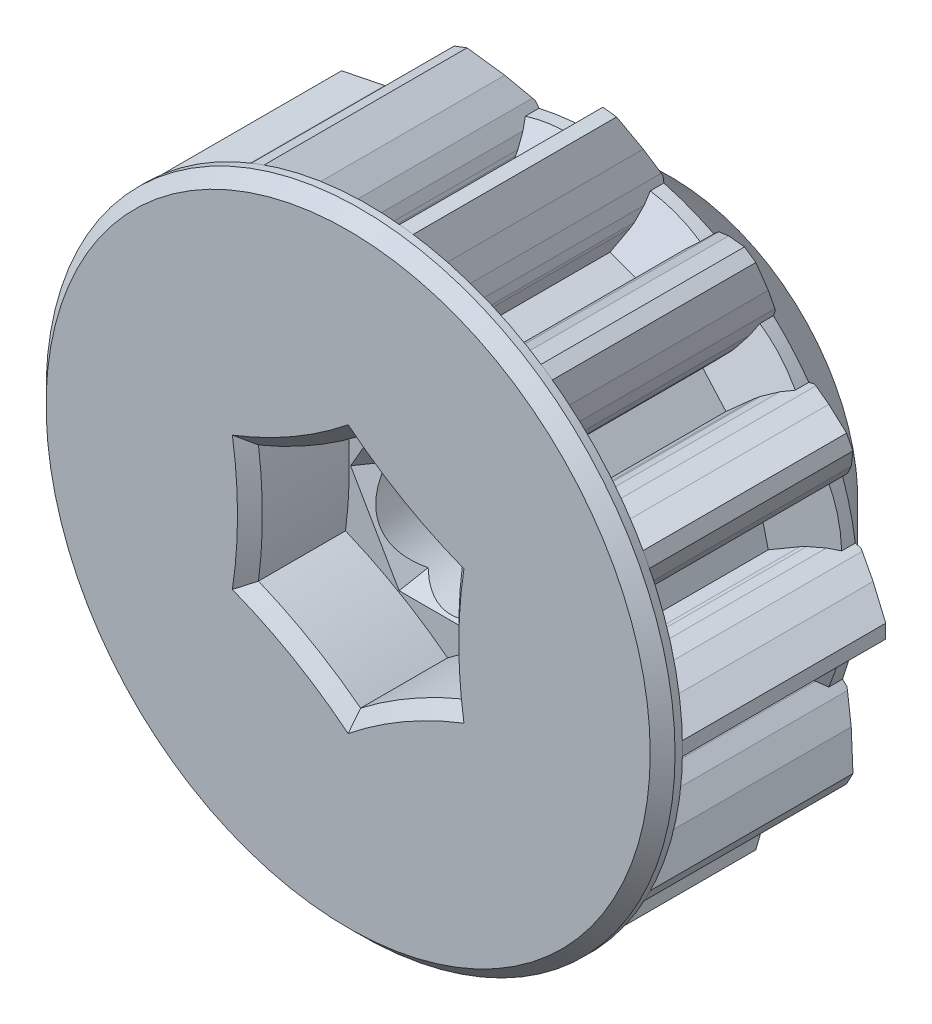
SolidWorks part; units mm, degrees
material "Custom Plastic"
ref_plane "Front Plane" through (0, 0, 0) normal (0, 0, 1) x (1, 0, 0)
ref_plane "Top Plane" through (0, 0, 0) normal (0, 1, 0) x (1, 0, 0)
ref_plane "Right Plane" through (0, 0, 0) normal (1, 0, 0) x (0, 0, -1)
sketch "Model" plane through (0, 0, 0) normal (0, 0, 1) x (1, 0, 0)
  line L0 (-12.322, -2.752) -> (-11.499, -1.837)
  line L1 (-11.499, -1.837) -> (-10.75, -1.243)
  line L2 (-10.75, -1.243) -> (-10.152, -0.913)
  line L3 (-10.152, -0.913) -> (-9.766, -0.777)
  line L4 (-9.766, -0.777) -> (-9.632, -0.751)
  line L5 (-9.632, -0.751) -> (-8.992, -0.701)
  line L6 (-8.992, -0.701) -> (-8.992, 0.701)
  line L7 (-8.992, 0.701) -> (-9.632, 0.751)
  line L8 (-9.632, 0.751) -> (-9.766, 0.777)
  line L9 (-9.766, 0.777) -> (-10.152, 0.913)
  line L10 (-10.152, 0.913) -> (-10.75, 1.243)
  line L11 (-10.75, 1.243) -> (-11.499, 1.837)
  line L12 (-11.499, 1.837) -> (-12.322, 2.752)
  line L13 (-12.322, 2.752) -> (-12.189, 3.29)
  line L14 (-12.189, 3.29) -> (-11.036, 3.717)
  line L15 (-11.036, 3.717) -> (-10.096, 3.895)
  line L16 (-10.096, 3.895) -> (-9.414, 3.91)
  line L17 (-9.414, 3.91) -> (-9.008, 3.851)
  line L18 (-9.008, 3.851) -> (-8.878, 3.811)
  line L19 (-8.878, 3.811) -> (-8.288, 3.558)
  line L20 (-8.288, 3.558) -> (-7.637, 4.8)
  line L21 (-7.637, 4.8) -> (-8.18, 5.141)
  line L22 (-8.18, 5.141) -> (-8.286, 5.226)
  line L23 (-8.286, 5.226) -> (-8.565, 5.527)
  line L24 (-8.565, 5.527) -> (-8.941, 6.096)
  line L25 (-8.941, 6.096) -> (-9.328, 6.971)
  line L26 (-9.328, 6.971) -> (-9.631, 8.163)
  line L27 (-9.631, 8.163) -> (-9.264, 8.577)
  line L28 (-9.264, 8.577) -> (-8.045, 8.42)
  line L29 (-8.045, 8.42) -> (-7.129, 8.141)
  line L30 (-7.129, 8.141) -> (-6.519, 7.837)
  line L31 (-6.519, 7.837) -> (-6.187, 7.596)
  line L32 (-6.187, 7.596) -> (-6.09, 7.501)
  line L33 (-6.09, 7.501) -> (-5.685, 7.002)
  line L34 (-5.685, 7.002) -> (-4.532, 7.799)
  line L35 (-4.532, 7.799) -> (-4.854, 8.354)
  line L36 (-4.854, 8.354) -> (-4.908, 8.478)
  line L37 (-4.908, 8.478) -> (-5.016, 8.874)
  line L38 (-5.016, 8.874) -> (-5.084, 9.553)
  line L39 (-5.084, 9.553) -> (-5.02, 10.508)
  line L40 (-5.02, 10.508) -> (-4.735, 11.704)
  line L41 (-4.735, 11.704) -> (-4.217, 11.9)
  line L42 (-4.217, 11.9) -> (-3.21, 11.194)
  line L43 (-3.21, 11.194) -> (-2.529, 10.522)
  line L44 (-2.529, 10.522) -> (-2.13, 9.968)
  line L45 (-2.13, 9.968) -> (-1.948, 9.601)
  line L46 (-1.948, 9.601) -> (-1.907, 9.471)
  line L47 (-1.907, 9.471) -> (-1.78, 8.842)
  line L48 (-1.78, 8.842) -> (-0.388, 9.011)
  line L49 (-0.388, 9.011) -> (-0.416, 9.652)
  line L50 (-0.416, 9.652) -> (-0.406, 9.788)
  line L51 (-0.406, 9.788) -> (-0.317, 10.189)
  line L52 (-0.317, 10.189) -> (-0.062, 10.821)
  line L53 (-0.062, 10.821) -> (0.438, 11.637)
  line L54 (0.438, 11.637) -> (1.246, 12.563)
  line L55 (1.246, 12.563) -> (1.796, 12.497)
  line L56 (1.796, 12.497) -> (2.36, 11.404)
  line L57 (2.36, 11.404) -> (2.65, 10.492)
  line L58 (2.65, 10.492) -> (2.746, 9.817)
  line L59 (2.746, 9.817) -> (2.737, 9.407)
  line L60 (2.737, 9.407) -> (2.713, 9.273)
  line L61 (2.713, 9.273) -> (2.533, 8.657)
  line L62 (2.533, 8.657) -> (3.845, 8.16)
  line L63 (3.845, 8.16) -> (4.118, 8.74)
  line L64 (4.118, 8.74) -> (4.189, 8.856)
  line L65 (4.189, 8.856) -> (4.454, 9.169)
  line L66 (4.454, 9.169) -> (4.974, 9.611)
  line L67 (4.974, 9.611) -> (5.796, 10.101)
  line L68 (5.796, 10.101) -> (6.942, 10.545)
  line L69 (6.942, 10.545) -> (7.398, 10.23)
  line L70 (7.398, 10.23) -> (7.389, 9.001)
  line L71 (7.389, 9.001) -> (7.222, 8.059)
  line L72 (7.222, 8.059) -> (6.994, 7.416)
  line L73 (6.994, 7.416) -> (6.795, 7.057)
  line L74 (6.795, 7.057) -> (6.712, 6.949)
  line L75 (6.712, 6.949) -> (6.266, 6.487)
  line L76 (6.266, 6.487) -> (7.196, 5.438)
  line L77 (7.196, 5.438) -> (7.708, 5.825)
  line L78 (7.708, 5.825) -> (7.825, 5.895)
  line L79 (7.825, 5.895) -> (8.205, 6.049)
  line L80 (8.205, 6.049) -> (8.871, 6.198)
  line L81 (8.871, 6.198) -> (9.826, 6.25)
  line L82 (9.826, 6.25) -> (11.047, 6.111)
  line L83 (11.047, 6.111) -> (11.305, 5.62)
  line L84 (11.305, 5.62) -> (10.726, 4.536)
  line L85 (10.726, 4.536) -> (10.14, 3.779)
  line L86 (10.14, 3.779) -> (9.639, 3.316)
  line L87 (9.639, 3.316) -> (9.296, 3.091)
  line L88 (9.296, 3.091) -> (9.173, 3.034)
  line L89 (9.173, 3.034) -> (8.563, 2.832)
  line L90 (8.563, 2.832) -> (8.899, 1.471)
  line L91 (8.899, 1.471) -> (9.532, 1.576)
  line L92 (9.532, 1.576) -> (9.668, 1.583)
  line L93 (9.668, 1.583) -> (10.076, 1.543)
  line L94 (10.076, 1.543) -> (10.735, 1.366)
  line L95 (10.735, 1.366) -> (11.605, 0.968)
  line L96 (11.605, 0.968) -> (12.622, 0.277)
  line L97 (12.622, 0.277) -> (12.622, -0.277)
  line L98 (12.622, -0.277) -> (11.605, -0.968)
  line L99 (11.605, -0.968) -> (10.735, -1.366)
  line L100 (10.735, -1.366) -> (10.076, -1.543)
  line L101 (10.076, -1.543) -> (9.668, -1.583)
  line L102 (9.668, -1.583) -> (9.532, -1.576)
  line L103 (9.532, -1.576) -> (8.899, -1.471)
  line L104 (8.899, -1.471) -> (8.563, -2.832)
  line L105 (8.563, -2.832) -> (9.173, -3.034)
  line L106 (9.173, -3.034) -> (9.296, -3.091)
  line L107 (9.296, -3.091) -> (9.639, -3.316)
  line L108 (9.639, -3.316) -> (10.14, -3.779)
  line L109 (10.14, -3.779) -> (10.726, -4.536)
  line L110 (10.726, -4.536) -> (11.305, -5.62)
  line L111 (11.305, -5.62) -> (11.047, -6.111)
  line L112 (11.047, -6.111) -> (9.826, -6.25)
  line L113 (9.826, -6.25) -> (8.871, -6.198)
  line L114 (8.871, -6.198) -> (8.205, -6.049)
  line L115 (8.205, -6.049) -> (7.825, -5.895)
  line L116 (7.825, -5.895) -> (7.708, -5.825)
  line L117 (7.708, -5.825) -> (7.196, -5.438)
  line L118 (7.196, -5.438) -> (6.266, -6.487)
  line L119 (6.266, -6.487) -> (6.712, -6.949)
  line L120 (6.712, -6.949) -> (6.795, -7.057)
  line L121 (6.795, -7.057) -> (6.994, -7.416)
  line L122 (6.994, -7.416) -> (7.222, -8.059)
  line L123 (7.222, -8.059) -> (7.389, -9.001)
  line L124 (7.389, -9.001) -> (7.398, -10.23)
  line L125 (7.398, -10.23) -> (6.942, -10.545)
  line L126 (6.942, -10.545) -> (5.796, -10.101)
  line L127 (5.796, -10.101) -> (4.974, -9.611)
  line L128 (4.974, -9.611) -> (4.454, -9.169)
  line L129 (4.454, -9.169) -> (4.189, -8.856)
  line L130 (4.189, -8.856) -> (4.118, -8.74)
  line L131 (4.118, -8.74) -> (3.845, -8.16)
  line L132 (3.845, -8.16) -> (2.533, -8.657)
  line L133 (2.533, -8.657) -> (2.713, -9.273)
  line L134 (2.713, -9.273) -> (2.737, -9.407)
  line L135 (2.737, -9.407) -> (2.746, -9.817)
  line L136 (2.746, -9.817) -> (2.65, -10.492)
  line L137 (2.65, -10.492) -> (2.36, -11.404)
  line L138 (2.36, -11.404) -> (1.796, -12.497)
  line L139 (1.796, -12.497) -> (1.246, -12.563)
  line L140 (1.246, -12.563) -> (0.438, -11.637)
  line L141 (0.438, -11.637) -> (-0.062, -10.821)
  line L142 (-0.062, -10.821) -> (-0.317, -10.189)
  line L143 (-0.317, -10.189) -> (-0.406, -9.788)
  line L144 (-0.406, -9.788) -> (-0.416, -9.652)
  line L145 (-0.416, -9.652) -> (-0.388, -9.011)
  line L146 (-0.388, -9.011) -> (-1.78, -8.842)
  line L147 (-1.78, -8.842) -> (-1.907, -9.471)
  line L148 (-1.907, -9.471) -> (-1.948, -9.601)
  line L149 (-1.948, -9.601) -> (-2.13, -9.968)
  line L150 (-2.13, -9.968) -> (-2.529, -10.522)
  line L151 (-2.529, -10.522) -> (-3.21, -11.194)
  line L152 (-3.21, -11.194) -> (-4.217, -11.9)
  line L153 (-4.217, -11.9) -> (-4.735, -11.704)
  line L154 (-4.735, -11.704) -> (-5.02, -10.508)
  line L155 (-5.02, -10.508) -> (-5.084, -9.553)
  line L156 (-5.084, -9.553) -> (-5.016, -8.874)
  line L157 (-5.016, -8.874) -> (-4.908, -8.478)
  line L158 (-4.908, -8.478) -> (-4.854, -8.354)
  line L159 (-4.854, -8.354) -> (-4.532, -7.799)
  line L160 (-4.532, -7.799) -> (-5.685, -7.002)
  line L161 (-5.685, -7.002) -> (-6.09, -7.501)
  line L162 (-6.09, -7.501) -> (-6.187, -7.596)
  line L163 (-6.187, -7.596) -> (-6.519, -7.837)
  line L164 (-6.519, -7.837) -> (-7.129, -8.141)
  line L165 (-7.129, -8.141) -> (-8.045, -8.42)
  line L166 (-8.045, -8.42) -> (-9.264, -8.577)
  line L167 (-9.264, -8.577) -> (-9.631, -8.163)
  line L168 (-9.631, -8.163) -> (-9.328, -6.971)
  line L169 (-9.328, -6.971) -> (-8.941, -6.096)
  line L170 (-8.941, -6.096) -> (-8.565, -5.527)
  line L171 (-8.565, -5.527) -> (-8.286, -5.226)
  line L172 (-8.286, -5.226) -> (-8.18, -5.141)
  line L173 (-8.18, -5.141) -> (-7.637, -4.8)
  line L174 (-7.637, -4.8) -> (-8.288, -3.558)
  line L175 (-8.288, -3.558) -> (-8.878, -3.811)
  line L176 (-8.878, -3.811) -> (-9.008, -3.851)
  line L177 (-9.008, -3.851) -> (-9.414, -3.91)
  line L178 (-9.414, -3.91) -> (-10.096, -3.895)
  line L179 (-10.096, -3.895) -> (-11.036, -3.717)
  line L180 (-11.036, -3.717) -> (-12.189, -3.29)
  line L181 (-12.189, -3.29) -> (-12.322, -2.752)
  line L182 (0, 0) -> (12.622, 0) construction
  line L183 (8.899, 1.471) -> (8.899, -1.471) construction
  line L184 (9.532, 1.576) -> (9.532, -1.576) construction
  line L185 (9.668, 1.583) -> (9.668, -1.583) construction
  line L186 (10.076, 1.543) -> (10.076, -1.543) construction
  line L187 (10.735, 1.366) -> (10.735, -1.366) construction
  line L188 (11.605, 0.968) -> (11.605, -0.968) construction
  circle A0 centre (0, 0) radius 1.5 construction
  dimension "D1" = 3
  dimension "D2" = 12.622
  dimension "D3" = 0.554
  dimension "D4" = 2.942
  dimension "D5" = 3.152
  dimension "D6" = 3.166
  dimension "D7" = 3.086
  dimension "D8" = 2.732
  dimension "D9" = 1.936
  dimension "D10" = 8.899
  dimension "D11" = 9.532
  dimension "D12" = 9.668
  dimension "D13" = 10.076
  dimension "D14" = 10.735
  dimension "D15" = 11.605
extrude "Boss-Extrude1" add sketch "Model" along normal blind 10
sketch "Sketch1" plane through (0, 0, 0) normal (0, 0, -1) x (-1, 0, 0)
  circle A0 centre (0, 0) radius 10.5
  dimension "D1" = 21
extrude "Boss-Extrude2" add sketch "Sketch1" along normal blind 3
sketch "Sketch6" plane through (0, 0, 10) normal (0, 0, 1) x (1, 0, 0)
  circle A0 centre (0, 0) radius 12.65
  dimension "D1" = 25.3
extrude "Boss-Extrude3" add sketch "Sketch6" against normal blind 0.8
chamfer "Chamfer1" distance 2 distance2 2 13 edges at (8.731, -2.1515, 0) (6.731, -5.9625, 0) (3.189, -8.4085, 0) (-1.084, -8.9265, 0) (-5.1085, -7.4005, 0) (-7.9625, -4.179, 0) (-8.992, 0, 0) (-7.9625, 4.179, 0) (-5.1085, 7.4005, 0) (-1.084, 8.9265, 0) (3.189, 8.4085, 0) (6.731, 5.9625, 0) (8.731, 2.1515, 0)
sketch "Sketch2" plane through (0, 0, 10) normal (0, 0, 1) x (1, 0, 0)
  circle A0 centre (0, 0) radius 3.3
  dimension "D1" = 6.6
extrude "Cut-Extrude1" cut sketch "Sketch2" against normal through all
sketch "Sketch3" plane through (0, 0, -3) normal (0, 0, -1) x (-1, 0, 0)
  circle A0 centre (0, 0) radius 5.15
  dimension "D1" = 10.3
extrude "Cut-Extrude2" cut sketch "Sketch3" against normal blind 4
sketch "Sketch4" plane through (0, 0, 10) normal (0, 0, 1) x (1, 0, 0)
  line L1 (3.9, 0) -> (1.95, 3.3775)
  line L2 (1.95, 3.3775) -> (-1.95, 3.3775)
  line L3 (-1.95, 3.3775) -> (-3.9, 0)
  line L4 (-3.9, 0) -> (-1.95, -3.3775)
  line L5 (-1.95, -3.3775) -> (1.95, -3.3775)
  line L6 (1.95, -3.3775) -> (3.9, 0)
  circle A0 centre (0, 0) radius 3.9 construction
  circle A1 centre (0, 0) radius 3.3775 construction
  dimension "D1" = 7.8
extrude "Cut-Extrude3" cut sketch "Sketch4" against normal offset from surface (5 mm away) 4 up to face at (-5.15, 0, 1)
sketch "Sketch5" plane through (0, 0, 10) normal (0, 0, 1) x (1, 0, 0)
  line L0 (0, 0) -> (11, 19.0526) construction
  line L1 (-3.95, 2.2805) -> (-3.95, -2.2805) construction
  line L2 (-3.95, -2.2805) -> (0, -4.5611) construction
  line L3 (0, -4.5611) -> (3.95, -2.2805) construction
  line L4 (3.95, -2.2805) -> (3.95, 2.2805) construction
  line L5 (3.95, 2.2805) -> (0, 4.5611) construction
  line L6 (0, 4.5611) -> (-3.95, 2.2805) construction
  line L7 (0, 0) -> (0, 6.6728) construction
  line L8 (0, 0) -> (8.0758, 4.6625) construction
  circle A0 centre (0, 0) radius 3.95 construction
  arc A1 (0, 4.7416) -> (4.1064, 2.3708) centre (11, 19.0526) ccw
  arc A2 (4.1064, 2.3708) -> (4.1064, -2.3708) centre (22, 0) ccw
  arc A3 (4.1064, -2.3708) -> (0, -4.7416) centre (11, -19.0526) ccw
  arc A4 (0, -4.7416) -> (-4.1064, -2.3708) centre (-11, -19.0526) ccw
  arc A5 (-4.1064, -2.3708) -> (-4.1064, 2.3708) centre (-22, 0) ccw
  arc A6 (-4.1064, 2.3708) -> (0, 4.7416) centre (-11, 19.0526) ccw
  point P35 (0, 0)
  dimension "D1" = 7.9
  dimension "D3" = 22
  dimension "D2" = 6
extrude "Cut-Extrude4" cut sketch "Sketch5" against normal blind 4
chamfer "Chamfer4" distance 3 angle 45 1 edges at (-10.5, 0, -3)
chamfer "Chamfer5" distance 2 distance2 1 13 edges at (1.521, 12.53, 0) (7.17, 10.3875, 0) (11.176, 5.8655, 0) (12.622, 0, 0) (11.176, -5.8655, 0) (7.17, -10.3875, 0) (1.521, -12.53, 0) (-4.476, -11.802, 0) (-9.4475, -8.37, 0) (-12.2555, -3.021, 0) (-12.2555, 3.021, 0) (-9.4475, 8.37, 0) (-4.476, 11.802, 0) first distance on face at (1.3684, 11.27, 0) first distance on face at (6.4491, 9.3433, 0) first distance on face at (10.0525, 5.2757, 0) first distance on face at (11.3528, 0, 0) first distance on face at (10.0525, -5.2757, 0) first distance on face at (6.4491, -9.3433, 0) first distance on face at (1.3684, -11.27, 0) first distance on face at (-4.0257, -10.6152, 0) first distance on face at (-8.4976, -7.5283, 0) first distance on face at (-11.0229, -2.7169, 0) first distance on face at (-11.0229, 2.7169, 0) first distance on face at (-8.4976, 7.5283, 0) first distance on face at (-4.0257, 10.6152, 0)
chamfer "Chamfer6" distance 0.5 angle 45 7 edges at (12.65, 0, 10) (3.95, 0, 10) (1.975, 3.4208, 10) (-1.975, 3.4208, 10) (-3.95, 0, 10) (-1.975, -3.4208, 10) (1.975, -3.4208, 10)
chamfer "Chamfer7" distance 1 angle 60 13 edges at (-7.9625, -4.179, 9.2) (-5.1085, -7.4005, 9.2) (-1.084, -8.9265, 9.2) (3.189, -8.4085, 9.2) (6.731, -5.9625, 9.2) (8.731, -2.1515, 9.2) (8.731, 2.1515, 9.2) (6.731, 5.9625, 9.2) (3.189, 8.4085, 9.2) (-1.084, 8.9265, 9.2) (-5.1085, 7.4005, 9.2) (-7.9625, 4.179, 9.2) (-8.992, 0, 9.2) first distance on face at (-7.9625, -4.179, 5.6) first distance on face at (-5.1085, -7.4005, 5.6) first distance on face at (-1.084, -8.9265, 5.6) first distance on face at (3.189, -8.4085, 5.6) first distance on face at (6.731, -5.9625, 5.6) first distance on face at (8.731, -2.1515, 5.6) first distance on face at (8.731, 2.1515, 5.6) first distance on face at (6.731, 5.9625, 5.6) first distance on face at (3.189, 8.4085, 5.6) first distance on face at (-1.084, 8.9265, 5.6) first distance on face at (-5.1085, 7.4005, 5.6) first distance on face at (-7.9625, 4.179, 5.6) first distance on face at (-8.992, 0, 5.6)
chamfer "Chamfer8" distance 1 distance2 0.6 6 edges at (0, -3.3775, 5) (2.925, -1.6887, 5) (2.925, 1.6887, 5) (0, 3.3775, 5) (-2.925, 1.6887, 5) (-2.925, -1.6887, 5) first distance on face at (0, -3.3775, 5.5) first distance on face at (2.925, -1.6887, 5.5) first distance on face at (2.925, 1.6887, 5.5) first distance on face at (0, 3.3775, 5.5) first distance on face at (-2.925, 1.6887, 5.5) first distance on face at (-2.925, -1.6887, 5.5)
chamfer "Chamfer9" distance 0.5 angle 45 1 edges at (-5.15, 0, -3)
